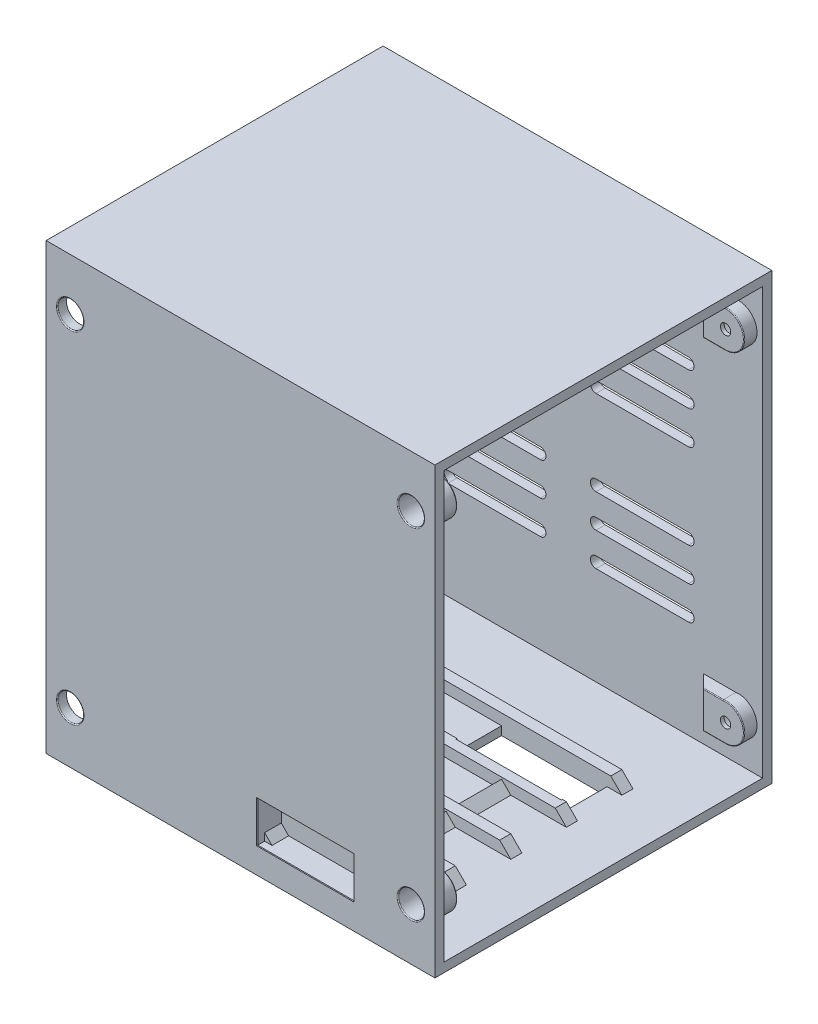
SolidWorks part; units mm, degrees
ref_plane "Front Plane" through (0, 0, 0) normal (0, 0, 1) x (1, 0, 0)
ref_plane "Top Plane" through (0, 0, 0) normal (0, 1, 0) x (1, 0, 0)
ref_plane "Right Plane" through (0, 0, 0) normal (1, 0, 0) x (0, 0, -1)
sketch "Sketch1" plane through (205.5525, 0, 0) normal (1, 0, 0) x (0, 0, -1)
  line L0 (1.5129, 48.8646) -> (1.513, -71.1354) construction
  line L1 (-89.4871, 48.8644) -> (1.5129, 48.8646) construction
  line L2 (-89.4871, 48.8644) -> (-89.487, -71.1356) construction
  line L3 (-89.487, -71.1356) -> (1.513, -71.1354) construction
  line L4 (1.5129, 48.8646) -> (1.513, -71.1354)
  line L5 (-89.4871, 48.8644) -> (1.5129, 48.8646)
  line L6 (-89.4871, 48.8644) -> (-89.487, -71.1356)
  line L7 (-89.487, -71.1356) -> (1.513, -71.1354)
  line L8 (-86.987, -68.6356) -> (-0.987, -68.6355)
  line L9 (-0.9871, 46.3645) -> (-0.987, -68.6355)
  line L10 (-86.9871, 46.3644) -> (-0.9871, 46.3645)
  line L11 (-86.9871, 46.3644) -> (-86.987, -68.6356)
  dimension "D1" = 2.5
extrude "Boss-Extrude1" add sketch "Sketch1" along normal up to surface (105 mm away)
sketch "Sketch2" plane through (0, 0, 86.9871) normal (0, 0, -1) x (-1, 0, 0)
  line L0 (-205.5525, 46.3645) -> (-205.5525, -68.6355) construction
  line L1 (-208.4525, -46.1353) -> (-206.5525, -46.1353)
  line L2 (-208.4525, -46.1353) -> (-208.4525, -40.1355)
  line L3 (-208.4525, -40.1355) -> (-206.5525, -40.1355)
  line L4 (-206.5525, -46.1353) -> (-206.5525, -40.1355)
  line L5 (-206.5525, 23.8645) -> (-208.4525, 23.8645)
  line L6 (-206.5525, 23.8645) -> (-206.5525, 17.8647)
  line L7 (-206.5525, 17.8647) -> (-208.4525, 17.8647)
  line L8 (-208.4525, 23.8645) -> (-208.4525, 17.8647)
  dimension "D1" = 0.1
  dimension "D2" = 1
  dimension "D3" = 0.1
  dimension "D4" = 1
  dimension "D5" = 0
  dimension "D6" = 0
  dimension "D7" = 0
  dimension "D8" = 0
extrude "Boss-Extrude2" add sketch "Sketch2" along normal offset from surface (1.3 mm away) 0.2
sketch "Sketch3" plane through (0, 0, 0.9871) normal (0, 0, 1) x (1, 0, 0)
  line L1 (210.0525, 28.8645) -> (225.0525, 28.8645)
  line L2 (210.0525, 28.8645) -> (210.0525, -51.1355)
  line L3 (210.0525, -51.1355) -> (225.0525, -51.1355)
  line L4 (225.0525, 28.8645) -> (225.0525, -51.1355)
  line L6 (205.5525, -68.6355) -> (205.5525, 46.3645) construction
  line L7 (310.5525, -71.1355) -> (205.5525, -71.1355) construction
  line L8 (310.5525, 48.8645) -> (205.5525, 48.8645) construction
  dimension "D1" = 4.5
  dimension "D2" = 15
  dimension "D3" = 20
  dimension "D4" = 20
extrude "Cut-Extrude1" cut sketch "Sketch3" against normal blind 0.5
sketch "Sketch4" plane through (0, 0, 0.9871) normal (0, 0, 1) x (1, 0, 0)
  line L0 (212.0525, 39.8645) -> (205.5525, 39.8645)
  line L1 (205.5525, -68.6355) -> (205.5525, 46.3645) construction
  line L2 (212.0525, 29.8645) -> (205.5525, 29.8645)
  line L3 (205.5525, 29.8645) -> (205.5525, 39.8645)
  line L4 (212.0525, -52.1355) -> (205.5525, -52.1355)
  line L5 (212.0525, -62.1355) -> (205.5525, -62.1355)
  line L6 (205.5525, -62.1355) -> (205.5525, -52.1355)
  line L7 (304.0525, -62.1355) -> (294.0525, -62.1355)
  line L8 (294.0525, -62.1355) -> (294.0525, -52.1855)
  line L9 (304.1025, -52.1855) -> (294.0525, -52.1855)
  line L10 (304.0525, 29.8645) -> (294.0525, 29.8645)
  line L11 (304.0525, 39.8645) -> (294.0525, 39.8645)
  line L12 (294.0525, 39.8645) -> (294.0525, 29.8645)
  circle A0 centre (212.0525, 34.8645) radius 2.25 construction
  circle A1 centre (212.0525, -57.1355) radius 2.25 construction
  circle A2 centre (212.0525, 34.8645) radius 2.25 construction
  circle A3 centre (212.0525, -57.1355) radius 2.25 construction
  circle A4 centre (212.0525, -57.1355) radius 5
  circle A5 centre (212.0525, 34.8645) radius 5
  circle A6 centre (212.0525, -57.1355) radius 3.5
  circle A7 centre (212.0525, 34.8645) radius 3.5
  circle A8 centre (212.0525, 34.8645) radius 1.4
  circle A9 centre (212.0525, -57.1355) radius 1.4
  circle A10 centre (304.0525, 34.8645) radius 1.6 construction
  circle A11 centre (304.0525, -57.1355) radius 1.6 construction
  circle A12 centre (304.0525, 34.8645) radius 1.6 construction
  circle A13 centre (304.0525, -57.1355) radius 1.6 construction
  circle A14 centre (304.0525, 34.8645) radius 5
  circle A15 centre (304.0525, -57.1355) radius 5
  circle A16 centre (304.0525, -57.1355) radius 3.5
  circle A17 centre (304.0525, -57.1355) radius 1.4
  circle A18 centre (304.0525, 34.8645) radius 3.5
  circle A19 centre (304.0525, 34.8645) radius 1.4
  line M7 (205.5525, 46.3645) -> (205.5525, -68.6355)
  dimension "D1" = 10
  dimension "D2" = 10
  dimension "D3" = 7
  dimension "D4" = 7
  dimension "D5" = 2.8
  dimension "D6" = 2.8
  dimension "D7" = 10
  dimension "D8" = 7
  dimension "D9" = 2.8
  dimension "D10" = 10
  dimension "D11" = 7
  dimension "D12" = 2.8
  dimension "D13" = 10
  dimension "D14" = 10
extrude "Boss-Extrude3" add sketch "Sketch4" along normal up to surface (3.5 mm away) contours A5 A7 | A4 A6 | A5 L0 L2 M7 | A4 L4 L5 M7 | A15 A16 | A14 A18 | A14 L11 L12 L10 | A15 L9 L8 L7 region at (206.9332, 34.8645, 0.9871) region at (208.8025, -52.2547, 0.9871) region at (215.488, 38.3001, 0.9871) region at (215.488, -53.6999, 0.9871) region at (299.2061, -57.479, 0.9871) region at (297.1787, -57.1748, 0.9871) region at (297.1915, 34.8645, 0.9871) region at (299.1939, 34.8645, 0.9871)
extrude "Boss-Extrude4" add sketch "Sketch4<3>" against normal blind 1 from surface contours A7 A8 | A18 A19 | A16 A17 | A6 A9 region at (208.6515, -57.1355, 0.9871) region at (208.6515, 34.8645, 0.9871) region at (300.6515, -57.1355, 0.9871) region at (300.6515, 34.8645, 0.9871) starting at face at (307.5525, 34.8645, 4.4871)
sketch "Sketch4<3>" plane through (0, 0, 0.9871) normal (0, 0, 1) x (1, 0, 0) same geometry as "Sketch4"
extrude "Cut-Extrude2" cut sketch "Sketch4<4>" against normal through all contours A6 A9 | A9 | A7 A8 | A8 | A17 | A16 A17 | A19 | A18 A19 region at (208.6515, -57.1355, 0.9871) region at (208.6515, 34.8645, 0.9871) region at (212.0525, 34.8645, 0.9871) region at (212.0525, -57.1355, 0.9871) region at (300.6515, -57.1355, 0.9871) region at (304.0525, -57.1355, 0.9871) region at (300.6515, 34.8645, 0.9871) region at (304.0525, 34.8645, 0.9871)
sketch "Sketch4<4>" plane through (0, 0, 0.9871) normal (0, 0, 1) x (1, 0, 0) same geometry as "Sketch4"
chamfer "Chamfer1" distance 4 angle 45 1 edges at (294.0525, -57.1605, 4.4871)
chamfer "Chamfer2" distance 4 angle 45 1 edges at (294.0525, 34.8645, 4.4871)
sketch "Sketch5" plane through (0, 0, -1.5129) normal (0, 0, -1) x (-1, 0, 0)
  line L0 (-258.0525, 48.8645) -> (-258.0525, -71.1355) construction
  line L1 (-310.5525, 48.8645) -> (-205.5525, 48.8645) construction
  line L2 (-310.5525, -71.1355) -> (-205.5525, -71.1355) construction
  line L3 (-310.5525, -11.1355) -> (-205.5525, -11.1355) construction
  line L4 (-310.5525, -71.1355) -> (-310.5525, 48.8645) construction
  line L5 (-205.5525, 48.8645) -> (-205.5525, -71.1355) construction
  line L6 (-290.5525, 10.8645) -> (-290.5525, 7.8645)
  line L7 (-290.5525, 1.8645) -> (-265.5525, 1.8645)
  line L8 (-290.5525, 1.8645) -> (-290.5525, -1.1355)
  line L9 (-290.5525, -1.1355) -> (-265.5525, -1.1355)
  line L10 (-265.5525, 1.8645) -> (-265.5525, -1.1355)
  line L11 (-290.5525, 10.8645) -> (-265.5525, 10.8645)
  line L12 (-265.5525, 10.8645) -> (-265.5525, 7.8645)
  line L13 (-290.5525, 7.8645) -> (-265.5525, 7.8645)
  line L14 (-290.5525, 19.8645) -> (-290.5525, 16.8645)
  line L15 (-290.5525, 19.8645) -> (-265.5525, 19.8645)
  line L16 (-265.5525, 19.8645) -> (-265.5525, 16.8645)
  line L17 (-290.5525, 16.8645) -> (-265.5525, 16.8645)
  line L18 (-225.5525, 16.8645) -> (-250.5525, 16.8645)
  line L19 (-250.5525, 19.8645) -> (-250.5525, 16.8645)
  line L20 (-225.5525, 19.8645) -> (-250.5525, 19.8645)
  line L21 (-225.5525, 19.8645) -> (-225.5525, 16.8645)
  line L22 (-225.5525, 7.8645) -> (-250.5525, 7.8645)
  line L23 (-250.5525, 10.8645) -> (-250.5525, 7.8645)
  line L24 (-225.5525, 10.8645) -> (-250.5525, 10.8645)
  line L25 (-250.5525, 1.8645) -> (-250.5525, -1.1355)
  line L26 (-225.5525, -1.1355) -> (-250.5525, -1.1355)
  line L27 (-225.5525, 1.8645) -> (-225.5525, -1.1355)
  line L28 (-225.5525, 1.8645) -> (-250.5525, 1.8645)
  line L29 (-225.5525, 10.8645) -> (-225.5525, 7.8645)
  line L30 (-225.5525, -33.1355) -> (-225.5525, -30.1355)
  line L31 (-225.5525, -24.1355) -> (-250.5525, -24.1355)
  line L32 (-225.5525, -24.1355) -> (-225.5525, -21.1355)
  line L33 (-225.5525, -21.1355) -> (-250.5525, -21.1355)
  line L34 (-250.5525, -24.1355) -> (-250.5525, -21.1355)
  line L35 (-225.5525, -33.1355) -> (-250.5525, -33.1355)
  line L36 (-250.5525, -33.1355) -> (-250.5525, -30.1355)
  line L37 (-225.5525, -30.1355) -> (-250.5525, -30.1355)
  line L38 (-225.5525, -42.1355) -> (-225.5525, -39.1355)
  line L39 (-225.5525, -42.1355) -> (-250.5525, -42.1355)
  line L40 (-250.5525, -42.1355) -> (-250.5525, -39.1355)
  line L41 (-225.5525, -39.1355) -> (-250.5525, -39.1355)
  line L42 (-290.5525, -39.1355) -> (-265.5525, -39.1355)
  line L43 (-265.5525, -42.1355) -> (-265.5525, -39.1355)
  line L44 (-290.5525, -42.1355) -> (-265.5525, -42.1355)
  line L45 (-290.5525, -42.1355) -> (-290.5525, -39.1355)
  line L46 (-290.5525, -30.1355) -> (-265.5525, -30.1355)
  line L47 (-265.5525, -33.1355) -> (-265.5525, -30.1355)
  line L48 (-290.5525, -33.1355) -> (-265.5525, -33.1355)
  line L49 (-265.5525, -24.1355) -> (-265.5525, -21.1355)
  line L50 (-290.5525, -21.1355) -> (-265.5525, -21.1355)
  line L51 (-290.5525, -24.1355) -> (-290.5525, -21.1355)
  line L52 (-290.5525, -24.1355) -> (-265.5525, -24.1355)
  line L53 (-290.5525, -33.1355) -> (-290.5525, -30.1355)
  arc A0 (-265.5525, 1.8645) -> (-265.5525, -1.1355) centre (-265.5525, 0.3645) cw
  arc A1 (-290.5525, -1.1355) -> (-290.5525, 1.8645) centre (-290.5525, 0.3645) cw
  arc A2 (-265.5525, 10.8645) -> (-265.5525, 7.8645) centre (-265.5525, 9.3645) cw
  arc A3 (-290.5525, 7.8645) -> (-290.5525, 10.8645) centre (-290.5525, 9.3645) cw
  arc A4 (-265.5525, 19.8645) -> (-265.5525, 16.8645) centre (-265.5525, 18.3645) cw
  arc A5 (-290.5525, 16.8645) -> (-290.5525, 19.8645) centre (-290.5525, 18.3645) cw
  arc A6 (-225.5525, 16.8645) -> (-225.5525, 19.8645) centre (-225.5525, 18.3645) ccw
  arc A7 (-250.5525, 19.8645) -> (-250.5525, 16.8645) centre (-250.5525, 18.3645) ccw
  arc A8 (-225.5525, 7.8645) -> (-225.5525, 10.8645) centre (-225.5525, 9.3645) ccw
  arc A9 (-250.5525, 10.8645) -> (-250.5525, 7.8645) centre (-250.5525, 9.3645) ccw
  arc A10 (-225.5525, -1.1355) -> (-225.5525, 1.8645) centre (-225.5525, 0.3645) ccw
  arc A11 (-250.5525, 1.8645) -> (-250.5525, -1.1355) centre (-250.5525, 0.3645) ccw
  arc A12 (-250.5525, -24.1355) -> (-250.5525, -21.1355) centre (-250.5525, -22.6355) cw
  arc A13 (-225.5525, -21.1355) -> (-225.5525, -24.1355) centre (-225.5525, -22.6355) cw
  arc A14 (-250.5525, -33.1355) -> (-250.5525, -30.1355) centre (-250.5525, -31.6355) cw
  arc A15 (-225.5525, -30.1355) -> (-225.5525, -33.1355) centre (-225.5525, -31.6355) cw
  arc A16 (-250.5525, -42.1355) -> (-250.5525, -39.1355) centre (-250.5525, -40.6355) cw
  arc A17 (-225.5525, -39.1355) -> (-225.5525, -42.1355) centre (-225.5525, -40.6355) cw
  arc A18 (-290.5525, -39.1355) -> (-290.5525, -42.1355) centre (-290.5525, -40.6355) ccw
  arc A19 (-265.5525, -42.1355) -> (-265.5525, -39.1355) centre (-265.5525, -40.6355) ccw
  arc A20 (-290.5525, -30.1355) -> (-290.5525, -33.1355) centre (-290.5525, -31.6355) ccw
  arc A21 (-265.5525, -33.1355) -> (-265.5525, -30.1355) centre (-265.5525, -31.6355) ccw
  arc A22 (-290.5525, -21.1355) -> (-290.5525, -24.1355) centre (-290.5525, -22.6355) ccw
  arc A23 (-265.5525, -24.1355) -> (-265.5525, -21.1355) centre (-265.5525, -22.6355) ccw
  dimension "D1" = 3
  dimension "D2" = 25
  dimension "D3" = 10
  dimension "D4" = 7.5
  dimension "D6" = 6
  dimension "D5" = 3
extrude "Cut-Extrude3" cut sketch "Sketch5" against normal blind 3 contours L14 L17 L16 L15 | A5 L14 | A4 L16 | A1 L8 | L10 L7 L8 L9 | A0 L10 | A2 L12 | L6 L13 L12 L11 | A3 L6 | A17 L38 | L38 L41 L40 L39 | A16 L40 | A14 L36 | L30 L37 L36 L35 | A15 L30 | A13 L32 | L34 L31 L32 L33 | A12 L34 | L51 A22 | L51 L52 L49 L50 | L49 A23 | L47 A21 | L53 L48 L47 L46 | L53 A20 | L45 A18 | L45 L44 L43 L42 | L43 A19 | L21 A6 | L21 L20 L19 L18 | L19 A7 | L23 A9 | L29 L24 L23 L22 | L29 A8 | L27 A10 | L27 L28 L25 L26 | L25 A11 region at (278.0525, 9.3645, -1.5129) region at (291.1891, 9.3645, -1.5129) region at (264.9159, 9.3645, -1.5129) region at (278.0525, 0.3645, -1.5129) region at (291.1891, 0.3645, -1.5129) region at (264.9159, 0.3645, -1.5129) region at (278.0525, 18.3645, -1.5129) region at (291.1891, 18.3645, -1.5129) region at (264.9159, 18.3645, -1.5129) region at (238.0525, 18.3645, -1.5129) region at (224.9159, 18.3645, -1.5129) region at (251.1891, 18.3645, -1.5129) region at (238.0525, 9.3645, -1.5129) region at (224.9159, 9.3645, -1.5129) region at (251.1891, 9.3645, -1.5129) region at (238.0525, 0.3645, -1.5129) region at (251.1891, 0.3645, -1.5129) region at (224.9159, 0.3645, -1.5129) region at (238.0525, -31.6355, -1.5129) region at (224.9159, -31.6355, -1.5129) region at (251.1891, -31.6355, -1.5129) region at (238.0525, -22.6355, -1.5129) region at (224.9159, -22.6355, -1.5129) region at (251.1891, -22.6355, -1.5129) region at (238.0525, -40.6355, -1.5129) region at (224.9159, -40.6355, -1.5129) region at (251.1891, -40.6355, -1.5129) region at (278.0525, -40.6355, -1.5129) region at (291.1891, -40.6355, -1.5129) region at (264.9159, -40.6355, -1.5129) region at (278.0525, -31.6355, -1.5129) region at (291.1891, -31.6355, -1.5129) region at (264.9159, -31.6355, -1.5129) region at (278.0525, -22.6355, -1.5129) region at (264.9159, -22.6355, -1.5129) region at (291.1891, -22.6355, -1.5129)
extrude "Boss-Extrude5" add sketch "Sketch4<6>" against normal up to surface (5 mm away) from surface contours A15 L9 L8 L7 | A15 A16 | A14 L11 L12 L10 | A14 A18 region at (299.2061, -57.479, 0.9871) region at (297.1787, -57.1748, 0.9871) region at (297.1915, 34.8645, 0.9871) region at (299.1939, 34.8645, 0.9871) starting at face at (258.0525, -11.1355, 86.9871)
sketch "Sketch4<6>" plane through (0, 0, 0.9871) normal (0, 0, 1) x (1, 0, 0) same geometry as "Sketch4"
extrude "Boss-Extrude6" add sketch "Sketch4<7>" along normal blind 1 from surface contours A14 A18 | A18 A19 | A16 A17 | A15 A16 region at (299.2061, -57.479, 0.9871) region at (299.1939, 34.8645, 0.9871) region at (300.6515, -57.1355, 0.9871) region at (300.6515, 34.8645, 0.9871) starting at face at (300.3025, 34.8645, 81.9871)
sketch "Sketch4<7>" plane through (0, 0, 0.9871) normal (0, 0, 1) x (1, 0, 0) same geometry as "Sketch4"
extrude "Cut-Extrude4" cut sketch "Sketch4<8>" along normal through all from surface contours A16 A17 | A18 A19 | A17 | A19 | A6 A9 | A9 | A7 A8 | A8 region at (208.6515, -57.1355, 0.9871) region at (208.6515, 34.8645, 0.9871) region at (212.0525, 34.8645, 0.9871) region at (212.0525, -57.1355, 0.9871) region at (300.6515, -57.1355, 0.9871) region at (304.0525, -57.1355, 0.9871) region at (300.6515, 34.8645, 0.9871) region at (304.0525, 34.8645, 0.9871) starting at face at (300.2112, -57.0658, 86.9871)
sketch "Sketch4<8>" plane through (0, 0, 0.9871) normal (0, 0, 1) x (1, 0, 0) same geometry as "Sketch4"
chamfer "Chamfer3" distance 5 angle 45 1 edges at (294.0525, -57.1605, 81.9871)
chamfer "Chamfer4" distance 5 angle 45 1 edges at (294.0525, 34.8645, 81.9871)
fillet "Fillet1" radius 0.25 9 edges at (307.5525, -57.1355, -1.5129) (307.5525, -57.1355, 3.4871) (307.5525, 34.8645, -1.5129) (215.5525, 34.8645, -1.5129) (215.5525, -57.1355, -1.5129) (304.0525, 38.3645, 89.4871) (212.0525, 38.3645, 89.4871) (212.0525, -53.6355, 89.4871) (304.0525, -53.6355, 89.4871)
sketch "Sketch6" plane through (0, -68.6355, 0) normal (0, 1, 0) x (1, 0, 0)
  line L0 (295.5525, -20.9871) -> (310.5525, -0.9871) construction
  line L1 (295.5525, -23.9871) -> (220.5525, -23.9871)
  line L2 (295.5525, -23.9871) -> (295.5525, -20.9871)
  line L3 (295.5525, -20.9871) -> (220.5525, -20.9871)
  line L4 (220.5525, -23.9871) -> (220.5525, -20.9871)
  line L5 (310.5525, -86.9871) -> (295.5525, -23.9871) construction
  line L6 (220.5525, -23.9871) -> (205.5525, -86.9871) construction
  line L7 (220.5525, -20.9871) -> (205.5525, -0.9871)
  line L8 (295.5525, -35.9871) -> (220.5525, -35.9871)
  line L9 (295.5525, -38.9871) -> (295.5525, -35.9871)
  line L10 (295.5525, -38.9871) -> (220.5525, -38.9871)
  line L11 (220.5525, -38.9871) -> (220.5525, -35.9871)
  line L12 (295.5525, -50.9871) -> (220.5525, -50.9871)
  line L13 (295.5525, -53.9871) -> (295.5525, -50.9871)
  line L14 (295.5525, -53.9871) -> (220.5525, -53.9871)
  line L15 (220.5525, -53.9871) -> (220.5525, -50.9871)
  line L41 (295.5525, -65.9871) -> (220.5525, -65.9871)
  line L42 (295.5525, -68.9871) -> (295.5525, -65.9871)
  line L43 (295.5525, -68.9871) -> (220.5525, -68.9871)
  line L44 (220.5525, -68.9871) -> (220.5525, -65.9871)
  dimension "D1" = 3
  dimension "D2" = 75
  dimension "D5" = 20
  dimension "D6" = 12
  dimension "D3" = 4
  dimension "D4" = 1
extrude "Boss-Extrude7" add sketch "Sketch6" along normal blind 3 contours L15 L14 L13 L12 | L11 L10 L9 L8 | L3 L2 L1 L4 | L41 L44 L43 L42 region at (258.0525, -68.6355, 37.4871) region at (258.0525, -68.6355, 52.4871)
chamfer "Chamfer5" distance 3 angle 45 8 edges at (295.5525, -65.6355, 37.4871) (295.5525, -65.6355, 22.4871) (220.5525, -65.6355, 22.4871) (220.5525, -65.6355, 37.4871) (220.5525, -65.6355, 52.4871) (295.5525, -65.6355, 52.4871) (220.5525, -65.6355, 67.4871) (295.5525, -65.6355, 67.4871)
sketch "Sketch7" plane through (0, -68.6355, 0) normal (0, 1, 0) x (1, 0, 0)
  line L1 (280.5525, -68.9871) -> (275.5525, -68.9871)
  line L2 (280.5525, -68.9871) -> (280.5525, -20.9871)
  line L3 (280.5525, -20.9871) -> (275.5525, -20.9871)
  line L4 (275.5525, -68.9871) -> (275.5525, -20.9871)
  line L6 (295.5525, -68.9871) -> (220.5525, -68.9871) construction
  line L7 (245.5525, -68.9871) -> (240.5525, -68.9871)
  line L8 (245.5525, -68.9871) -> (245.5525, -20.9871)
  line L9 (245.5525, -20.9871) -> (240.5525, -20.9871)
  line L10 (240.5525, -68.9871) -> (240.5525, -20.9871)
  line L11 (295.5525, -20.9871) -> (220.5525, -20.9871) construction
  line M2 (220.5525, -50.9871) -> (295.5525, -50.9871)
  line M4 (295.5525, -53.9871) -> (220.5525, -53.9871)
  line M8 (295.5525, -23.9871) -> (220.5525, -23.9871)
  line M18 (220.5525, -35.9871) -> (295.5525, -35.9871)
  line M20 (295.5525, -38.9871) -> (220.5525, -38.9871)
  line M37 (220.5525, -65.9871) -> (295.5525, -65.9871)
  dimension "D1" = 5
  dimension "D2" = 5
  dimension "D3" = 15
  dimension "D4" = 20
extrude "Boss-Extrude8" add sketch "Sketch7" along normal blind 2.5 contours L4 L2 M2 M20 | L4 L2 M18 M8 | L4 L2 M37 M4 | L10 L8 M37 M4 | L10 L8 M2 M20 | L10 L8 M18 M8 region at (278.0525, -68.6355, 59.9871) region at (243.0525, -68.6355, 59.9871) region at (278.0525, -68.6355, 44.9871) region at (243.0525, -68.6355, 44.9871) region at (278.0525, -68.6355, 29.9871) region at (243.0525, -68.6355, 29.9871)
chamfer "Chamfer6" distance 2.5 angle 45 12 edges at (240.5525, -66.1355, 59.9871) (245.5525, -66.1355, 59.9871) (240.5525, -66.1355, 44.9871) (245.5525, -66.1355, 44.9871) (240.5525, -66.1355, 29.9871) (245.5525, -66.1355, 29.9871) (275.5525, -66.1355, 29.9871) (280.5525, -66.1355, 29.9871) (275.5525, -66.1355, 44.9871) (280.5525, -66.1355, 44.9871) (275.5525, -66.1355, 59.9871) (280.5525, -66.1355, 59.9871)
extrude "Boss-Extrude9" add sketch "Sketch6<3>" against normal blind 3 from surface contours L4 L1 L2 L3 | L11 L10 L9 L8 | L15 L14 L13 L12 | L44 L43 L42 L41 region at (258.0525, -68.6355, 22.4871) region at (258.0525, -68.6355, 37.4871) region at (258.0525, -68.6355, 52.4871) region at (258.0525, -68.6355, 67.4871) starting at face at (258.0525, 46.3645, 43.9871)
sketch "Sketch6<3>" plane through (0, -68.6355, 0) normal (0, 1, 0) x (1, 0, 0) same geometry as "Sketch6"
sketch "Sketch8" plane through (0, 43.3645, 0) normal (0, -1, 0) x (1, 0, 0)
  line L1 (220.5525, 50.9871) -> (235.5525, 50.9871)
  line L2 (220.5525, 50.9871) -> (220.5525, 68.9871)
  line L3 (220.5525, 68.9871) -> (235.5525, 68.9871)
  line L4 (235.5525, 50.9871) -> (235.5525, 68.9871)
  line L5 (295.5525, 68.9871) -> (220.5525, 68.9871) construction
  dimension "D1" = 15
extrude "Cut-Extrude5" cut sketch "Sketch8" against normal up to surface (3 mm away) up to face at (258.0525, 46.3645, 22.4871)
chamfer "Chamfer7" distance 3 angle 45 8 edges at (295.5525, 43.3645, 52.4871) (235.5525, 43.3645, 52.4871) (295.5525, 43.3645, 22.4871) (220.5525, 43.3645, 22.4871) (220.5525, 43.3645, 37.4871) (295.5525, 43.3645, 37.4871) (235.5525, 43.3645, 67.4871) (295.5525, 43.3645, 67.4871)
extrude "Boss-Extrude10" add sketch "Sketch7<2>" against normal blind 2.5 from surface starting at face at (265.5525, 46.3645, 67.4871)
sketch "Sketch7<2>" plane through (0, -68.6355, 0) normal (0, 1, 0) x (1, 0, 0) same geometry as "Sketch7"
chamfer "Chamfer8" distance 2.5 angle 45 12 edges at (280.5525, 43.8645, 44.9871) (275.5525, 43.8645, 44.9871) (240.5525, 43.8645, 44.9871) (245.5525, 43.8645, 44.9871) (280.5525, 43.8645, 59.9871) (275.5525, 43.8645, 59.9871) (245.5525, 43.8645, 59.9871) (240.5525, 43.8645, 59.9871) (240.5525, 43.8645, 29.9871) (245.5525, 43.8645, 29.9871) (275.5525, 43.8645, 29.9871) (280.5525, 43.8645, 29.9871)
sketch "Sketch9" plane through (0, 0, 86.9871) normal (0, 0, -1) x (-1, 0, 0)
  line L0 (-310.5525, -68.6355) -> (-295.5525, -12.6355) construction
  line L1 (-295.5525, -9.6355) -> (-220.5525, -9.6355)
  line L2 (-295.5525, -9.6355) -> (-295.5525, -12.6355)
  line L3 (-295.5525, -12.6355) -> (-220.5525, -12.6355)
  line L4 (-220.5525, -9.6355) -> (-220.5525, -12.6355)
  line L5 (-310.5525, 46.3645) -> (-295.5525, -9.6355) construction
  line L6 (-205.5525, 46.3645) -> (-220.5525, -9.6355) construction
  line L7 (-205.5525, -68.6355) -> (-220.5525, -12.6355) construction
  line L8 (-295.5525, 5.3645) -> (-220.5525, 5.3645)
  line L9 (-295.5525, 2.3645) -> (-220.5525, 2.3645)
  line L10 (-295.5525, 5.3645) -> (-295.5525, 2.3645)
  line L11 (-220.5525, 5.3645) -> (-220.5525, 2.3645)
  line L12 (-295.5525, 20.3645) -> (-220.5525, 20.3645)
  line L13 (-295.5525, 17.3645) -> (-220.5525, 17.3645)
  line L14 (-295.5525, 20.3645) -> (-295.5525, 17.3645)
  line L15 (-220.5525, 20.3645) -> (-220.5525, 17.3645)
  line L16 (-295.5525, -9.6355) -> (-220.5525, -9.6355)
  line L17 (-295.5525, -12.6355) -> (-220.5525, -12.6355)
  line L18 (-295.5525, -9.6355) -> (-295.5525, -12.6355)
  line L19 (-220.5525, -9.6355) -> (-220.5525, -12.6355)
  line L20 (-295.5525, 5.3645) -> (-220.5525, 5.3645)
  line L21 (-295.5525, 2.3645) -> (-220.5525, 2.3645)
  line L22 (-295.5525, 5.3645) -> (-295.5525, 2.3645)
  line L23 (-220.5525, 5.3645) -> (-220.5525, 2.3645)
  line L24 (-295.5525, -24.6355) -> (-220.5525, -24.6355)
  line L25 (-295.5525, -27.6355) -> (-220.5525, -27.6355)
  line L26 (-295.5525, -24.6355) -> (-295.5525, -27.6355)
  line L27 (-220.5525, -24.6355) -> (-220.5525, -27.6355)
  line L28 (-295.5525, -9.6355) -> (-220.5525, -9.6355)
  line L29 (-295.5525, -12.6355) -> (-220.5525, -12.6355)
  line L30 (-295.5525, -9.6355) -> (-295.5525, -12.6355)
  line L31 (-220.5525, -9.6355) -> (-220.5525, -12.6355)
  line L32 (-295.5525, -24.6355) -> (-220.5525, -24.6355)
  line L33 (-295.5525, -27.6355) -> (-220.5525, -27.6355)
  line L34 (-295.5525, -24.6355) -> (-295.5525, -27.6355)
  line L35 (-220.5525, -24.6355) -> (-220.5525, -27.6355)
  line L36 (-295.5525, -39.6355) -> (-220.5525, -39.6355)
  line L37 (-295.5525, -42.6355) -> (-220.5525, -42.6355)
  line L38 (-295.5525, -39.6355) -> (-295.5525, -42.6355)
  line L39 (-220.5525, -39.6355) -> (-220.5525, -42.6355)
  dimension "D1" = 3
  dimension "D2" = 75
  dimension "D3" = 3
  dimension "D4" = 3
extrude "Boss-Extrude11" add sketch "Sketch9" along normal blind 3 contours L15 L12 L14 L13 | L11 L8 L10 L9 | L4 L1 L2 L3 | L27 L24 L26 L25 | L36 L39 L37 L38 region at (258.0525, -11.1355, 86.9871) region at (258.0525, 3.8645, 86.9871) region at (258.0525, 18.8645, 86.9871) region at (258.0525, -26.1355, 86.9871)
chamfer "Chamfer9" distance 3 angle 45 10 edges at (295.5525, 3.8645, 83.9871) (295.5525, -11.1355, 83.9871) (295.5525, -26.1355, 83.9871) (295.5525, -41.1355, 83.9871) (220.5525, -41.1355, 83.9871) (220.5525, -26.1355, 83.9871) (220.5525, -11.1355, 83.9871) (220.5525, 3.8645, 83.9871) (220.5525, 18.8645, 83.9871) (295.5525, 18.8645, 83.9871)
sketch "Sketch10" plane through (0, 0, 86.9871) normal (0, 0, -1) x (-1, 0, 0)
  line L0 (-295.5525, -42.6355) -> (-220.5525, -42.6355) construction
  line L1 (-280.5525, -42.6355) -> (-275.5525, -42.6355)
  line L2 (-280.5525, -42.6355) -> (-280.5525, 20.3645)
  line L3 (-280.5525, 20.3645) -> (-275.5525, 20.3645)
  line L4 (-275.5525, -42.6355) -> (-275.5525, 20.3645)
  line L5 (-295.5525, 20.3645) -> (-220.5525, 20.3645) construction
  line L7 (-240.5525, 20.3645) -> (-235.5525, 20.3645)
  line L8 (-240.5525, 20.3645) -> (-240.5525, -42.6355)
  line L9 (-240.5525, -42.6355) -> (-235.5525, -42.6355)
  line L10 (-235.5525, 20.3645) -> (-235.5525, -42.6355)
  dimension "D1" = 5
  dimension "D2" = 15
  dimension "D3" = 5
  dimension "D4" = 15
extrude "Boss-Extrude12" add sketch "Sketch10" along normal blind 2.5
chamfer "Chamfer10" distance 2.5 angle 45 16 edges at (240.5525, -33.6355, 84.4871) (235.5525, -33.6355, 84.4871) (235.5525, -18.6355, 84.4871) (240.5525, -18.6355, 84.4871) (240.5525, -3.6355, 84.4871) (235.5525, -3.6355, 84.4871) (235.5525, 11.3645, 84.4871) (240.5525, 11.3645, 84.4871) (275.5525, -3.6355, 84.4871) (275.5525, -18.6355, 84.4871) (275.5525, -33.6355, 84.4871) (280.5525, -33.6355, 84.4871) (280.5525, -18.6355, 84.4871) (280.5525, -3.6355, 84.4871) (275.5525, 11.3645, 84.4871) (280.5525, 11.3645, 84.4871)
sketch "Sketch11" plane through (0, -68.6355, 0) normal (0, 1, 0) x (1, 0, 0)
  line L1 (263.0525, -23.9871) -> (291.5525, -23.9871)
  line L2 (263.0525, -23.9871) -> (263.0525, -36.2871)
  line L3 (263.0525, -36.2871) -> (291.5525, -36.2871)
  line L4 (291.5525, -23.9871) -> (291.5525, -36.2871)
  line L6 (275.5525, -23.9871) -> (245.5525, -23.9871) construction
  line M33 (295.5525, -23.9871) -> (280.5525, -23.9871)
  line M35 (280.5525, -35.9871) -> (295.5525, -35.9871)
  line M36 (295.5525, -35.9871) -> (295.5525, -38.9871)
  line M47 (280.5525, -23.9871) -> (280.5525, -35.9871)
  dimension "D1" = 12.3
  dimension "D2" = 28.5
  dimension "D3" = 4
extrude "Cut-Extrude7" cut sketch "Sketch11" against normal blind 5 and the other way blind 4 contours L4 M33 M47 M35 | L2 L3 L1 M36 M35 M47 region at (272.0176, -68.6355, 30.2277) region at (286.0525, -68.6355, 29.9871)
chamfer "Chamfer11" distance 0.2 angle 45 4 edges at (263.0525, -71.1355, 30.1371) (277.3025, -71.1355, 23.9871) (291.5525, -71.1355, 30.1371) (277.3025, -71.1355, 36.2871)
sketch "Sketch13" plane through (0, 0, -1.5129) normal (0, 0, -1) x (-1, 0, 0)
  line L0 (-310.5525, 48.8645) -> (-288.0525, 36.3645) construction
  line L1 (-205.5525, 48.8645) -> (-228.0525, 36.3645) construction
  line L2 (-228.0525, -58.6355) -> (-205.5525, -71.1355) construction
  line L3 (-288.0525, -58.6355) -> (-310.5525, -71.1355) construction
  line L4 (-310.5525, 48.8645) -> (-205.5525, 48.8645) construction
  line L5 (-205.5525, -71.1355) -> (-205.5525, 48.8645) construction
  circle A0 centre (-228.0525, 36.3645) radius 5.15
  circle A1 centre (-228.0525, -58.6355) radius 5.15
  circle A2 centre (-288.0525, -58.6355) radius 5.15
  circle A3 centre (-288.0525, 36.3645) radius 5.15
  dimension "D3" = 10.3
  dimension "D1" = 12.5
  dimension "D2" = 22.5
extrude "Cut-Extrude8" cut sketch "Sketch13" against normal offset from surface (1.75 mm away) 0.75 up to face at (278.0525, -31.6355, 0.9871)
sketch "Sketch14" plane through (0, 0, 86.9871) normal (0, 0, -1) x (-1, 0, 0)
  line L0 (-310.5525, -68.6355) -> (-205.5525, -68.6355) construction
  line L1 (-290.5525, -51.1355) -> (-260.5525, -51.1355)
  line L2 (-290.5525, -51.1355) -> (-290.5525, -66.1355)
  line L3 (-290.5525, -66.1355) -> (-260.5525, -66.1355)
  line L4 (-260.5525, -51.1355) -> (-260.5525, -66.1355)
  line L5 (-310.5525, -68.6355) -> (-310.5525, 46.3645) construction
  dimension "D1" = 30
  dimension "D2" = 15
  dimension "D3" = 2.5
  dimension "D4" = 20
extrude "Boss-Extrude13" add sketch "Sketch14" along normal blind 6
chamfer "Chamfer12" distance 6 angle 45 1 edges at (260.5525, -58.6355, 86.9871)
sketch "Sketch15" plane through (0, 0, 80.9871) normal (0, 0, -1) x (-1, 0, 0)
  line L8 (-288.5525, -53.1355) -> (-288.5525, -64.1355)
  line L9 (-288.5525, -64.1355) -> (-262.5525, -64.1355)
  line L10 (-262.5525, -64.1355) -> (-262.5525, -53.1355)
  line L11 (-262.5525, -53.1355) -> (-288.5525, -53.1355)
  line L12 (-288.5525, -53.1355) -> (-288.5525, -64.1355)
  line L13 (-288.5525, -64.1355) -> (-262.5525, -64.1355)
  line L14 (-262.5525, -64.1355) -> (-262.5525, -53.1355)
  line L15 (-262.5525, -53.1355) -> (-288.5525, -53.1355)
  dimension "D1" = 2
extrude "Cut-Extrude9" cut sketch "Sketch15" along normal offset from surface (6.5 mm away) 2 from surface up to face at (275.5525, -58.6355, 80.9871) starting at face at (304.0525, 38.6145, 89.4871)
chamfer "Chamfer13" distance 0.15 angle 45 4 edges at (288.5525, -58.6355, 89.4871) (275.5525, -64.1355, 89.4871) (262.5525, -58.6355, 89.4871) (275.5525, -53.1355, 89.4871)
sketch "Sketch16" plane through (0, 0, 82.9871) normal (0, 0, 1) x (1, 0, 0)
  line L0 (262.5525, -53.1355) -> (262.5525, -55.1355)
  line L1 (262.5525, -64.1355) -> (262.5525, -53.1355) construction
  line L2 (262.5525, -55.1355) -> (264.5525, -53.1355)
  line L3 (262.5525, -53.1355) -> (288.5525, -53.1355) construction
  line L4 (264.5525, -53.1355) -> (262.5525, -53.1355)
  line L5 (262.5525, -64.1355) -> (262.5525, -62.1355)
  line L6 (262.5525, -62.1355) -> (264.5525, -64.1355)
  line L7 (288.5525, -64.1355) -> (262.5525, -64.1355) construction
  line L8 (264.5525, -64.1355) -> (262.5525, -64.1355)
  line L9 (288.5525, -64.1355) -> (288.5525, -62.1355)
  line L10 (288.5525, -53.1355) -> (288.5525, -64.1355) construction
  line L11 (288.5525, -62.1355) -> (286.5525, -64.1355)
  line L12 (286.5525, -64.1355) -> (288.5525, -64.1355)
  line L13 (288.5525, -55.1355) -> (286.5525, -53.1355)
  line L14 (286.5525, -53.1355) -> (288.5525, -53.1355)
  line L15 (288.5525, -53.1355) -> (288.5525, -55.1355)
  dimension "D1" = 2
extrude "Boss-Extrude14" add sketch "Sketch16" along normal offset from surface (4.5 mm away) 2 up to face at (275.5525, -58.6355, 89.4871)
fillet "Fillet2" radius 0.2 18 edges at (301.0525, 29.8645, 4.4871) (309.0525, 34.8645, 4.4871) (301.0525, -62.1355, 4.4871) (208.8025, 39.8645, 4.4871) (217.0525, 34.8645, 4.4871) (208.8025, -62.1355, 4.4871) (217.0525, -57.1355, 4.4871) (301.0525, 39.8645, 4.4871) (300.6998, -52.1855, 4.4871) (309.04, -56.7819, 4.4871) (208.8025, 29.8645, 4.4871) (208.8025, -52.1355, 4.4871) (301.5525, -62.1355, 81.9871) (301.5525, 39.8645, 81.9871) (301.5525, 29.8645, 81.9871) (301.1998, -52.1855, 81.9871) (309.04, -56.7819, 81.9871) (309.0525, 34.8645, 81.9871)
equation "\"R\"=9.03994"
equation "\"R_MOUNT_OUTER\"=10"
equation "\"D1@Sketch4\"=\"R_MOUNT_OUTER\""
equation "\"D2@Sketch4\"=\"R_MOUNT_OUTER\""
equation "\"R_MOUNT_INNER\"=7"
equation "\"D3@Sketch4\"=\"R_MOUNT_INNER\""
equation "\"D4@Sketch4\"=\"R_MOUNT_INNER\""
equation "\"R_SCREW\"= 2.8"
equation "\"D5@Sketch4\"=\"R_SCREW\""
equation "\"D6@Sketch4\"=\"R_SCREW\""
equation "\"D7@Sketch4\"=\"R_MOUNT_OUTER\""
equation "\"D8@Sketch4\"=\"R_MOUNT_INNER\""
equation "\"D9@Sketch4\"=\"R_SCREW\""
equation "\"D10@Sketch4\"=\"R_MOUNT_OUTER\""
equation "\"D11@Sketch4\"=\"R_MOUNT_INNER\""
equation "\"D12@Sketch4\"=\"R_SCREW\""
